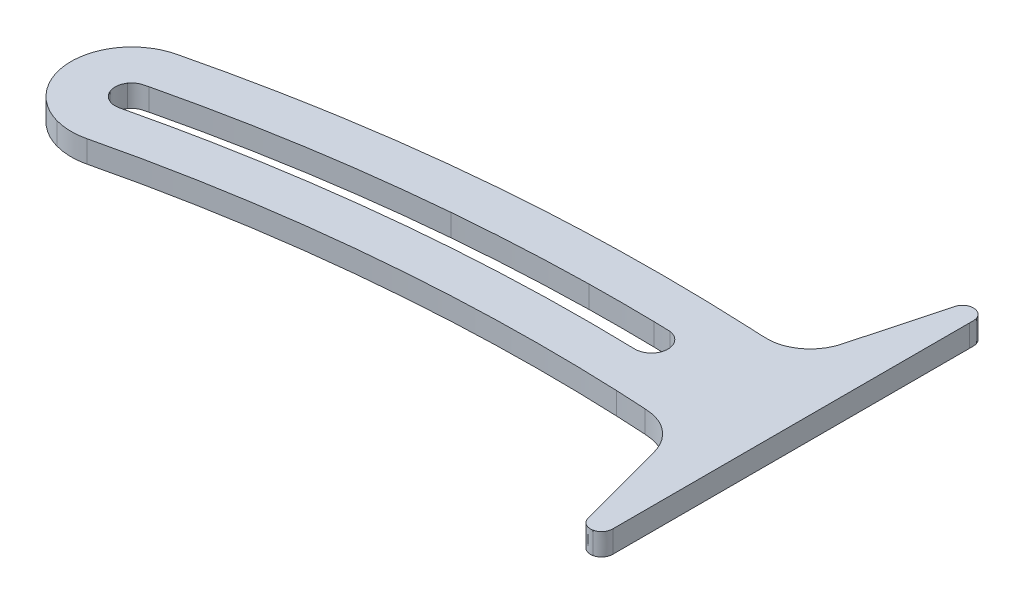
SolidWorks part; units mm, degrees
ref_plane "Front Plane" through (0, 0, 0) normal (0, 0, 1) x (1, 0, 0)
ref_plane "Top Plane" through (0, 0, 0) normal (0, 1, 0) x (1, 0, 0)
ref_plane "Right Plane" through (0, 0, 0) normal (1, 0, 0) x (0, 0, -1)
sketch "Imported Profile" plane through (0, 0, 0) normal (0, 1, 0) x (1, 0, 0)
  spline S0 degree 3 poles (12.8991, 25.236) (15.9171, 24.4093) (18.7007, 24.3473) (21.7531, 25.0501) knots 0 0 0 0 1 1 1 1
  spline S1 degree 3 poles (21.7531, 25.0501) (67.2422, 35.9573) (114.0335, 40.4773) (160.7696, 38.4929) knots 0 0 0 0 1 1 1 1
  spline S2 degree 3 poles (160.7696, 38.4929) (163.6635, 38.3689) (166.5574, 38.2174) (169.4444, 38.0449) knots 0 0 0 0 1 1 1 1
  spline S3 degree 3 poles (169.4444, 38.0449) (172.5863, 37.8589) (175.1081, 37.0734) (177.5541, 34.9719) knots 0 0 0 0 1 1 1 1
  spline S4 degree 3 poles (177.5541, 34.9719) (178.7254, 33.9728) (179.6419, 32.8428) (180.3929, 31.4993) knots 0 0 0 0 1 1 1 1
  spline S5 degree 3 poles (180.3929, 31.4993) (181.1026, 30.2177) (181.4953, 28.8603) (181.8674, 27.4685) knots 0 0 0 0 1 1 1 1
  spline S6 degree 3 poles (181.8674, 27.4685) (182.6184, 24.6642) (183.3694, 21.8599) (184.1205, 19.0625) knots 0 0 0 0 1 1 1 1
  spline S7 degree 3 poles (184.1205, 19.0625) (184.8715, 16.2582) (185.6225, 13.4539) (186.3735, 10.6495) knots 0 0 0 0 1 1 1 1
  spline S8 degree 3 poles (186.3735, 10.6495) (186.7457, 9.2508) (187.1246, 7.8521) (187.4967, 6.4465) knots 0 0 0 0 1 1 1 1
  spline S9 degree 3 poles (187.4967, 6.4465) (187.6827, 5.7506) (187.8756, 5.0478) (188.0617, 4.345) knots 0 0 0 0 1 1 1 1
  spline S10 degree 3 poles (188.0617, 4.345) (188.2477, 3.6491) (188.3786, 2.9463) (188.6335, 2.2642) knots 0 0 0 0 1 1 1 1
  spline S11 degree 3 poles (188.6335, 2.2642) (189.1847, 0.8172) (190.7006, -0.0165) (192.2233, 0.2798) knots 0 0 0 0 1 1 1 1
  spline S12 degree 3 poles (192.2233, 0.2798) (193.7874, 0.5968) (194.7796, 1.9335) (194.7796, 3.4975) knots 0 0 0 0 1 1 1 1
  spline S13 degree 3 poles (194.7796, 3.4975) (194.7796, 6.3983) (194.7796, 9.2991) (194.7796, 12.1998) knots 0 0 0 0 1 1 1 1
  spline S14 degree 3 poles (194.7796, 12.1998) (194.7796, 35.5507) (194.7796, 58.9084) (194.7796, 82.2593) knots 0 0 0 0 1 1 1 1
  spline S15 degree 3 poles (194.7796, 82.2593) (194.7796, 88.0608) (194.7796, 93.8624) (194.7796, 99.6708) knots 0 0 0 0 1 1 1 1
  spline S16 degree 3 poles (194.7796, 99.6708) (194.7796, 101.1178) (194.7796, 102.5716) (194.7796, 104.0185) knots 0 0 0 0 1 1 1 1
  spline S17 degree 3 poles (194.7796, 104.0185) (194.7796, 104.742) (194.7796, 105.4724) (194.7796, 106.1958) knots 0 0 0 0 1 1 1 1
  spline S18 degree 3 poles (194.7796, 106.1958) (194.7796, 106.9193) (194.8485, 107.6152) (194.6072, 108.3387) knots 0 0 0 0 1 1 1 1
  spline S19 degree 3 poles (194.6072, 108.3387) (194.1043, 109.7994) (192.6229, 110.6882) (191.0932, 110.4402) knots 0 0 0 0 1 1 1 1
  spline S20 degree 3 poles (191.0932, 110.4402) (190.2595, 110.3027) (189.6807, 109.9717) (189.1433, 109.3171) knots 0 0 0 0 1 1 1 1
  spline S21 degree 3 poles (189.1433, 109.3171) (188.6541, 108.7176) (188.5094, 108.0424) (188.3234, 107.3327) knots 0 0 0 0 1 1 1 1
  spline S22 degree 3 poles (188.3234, 107.3327) (186.8213, 101.731) (185.3193, 96.1292) (183.8172, 90.5206) knots 0 0 0 0 1 1 1 1
  spline S23 degree 3 poles (183.8172, 90.5206) (183.0662, 87.7232) (182.3909, 84.912) (181.5641, 82.1353) knots 0 0 0 0 1 1 1 1
  spline S24 degree 3 poles (181.5641, 82.1353) (180.7097, 79.2483) (178.8563, 76.7678) (176.3413, 75.121) knots 0 0 0 0 1 1 1 1
  spline S25 degree 3 poles (176.3413, 75.121) (172.2486, 72.4477) (169.1411, 73.0678) (164.7796, 73.2676) knots 0 0 0 0 1 1 1 1
  spline S26 degree 3 poles (164.7796, 73.2676) (145.3906, 74.1909) (126.0843, 74.1289) (106.7022, 73.0126) knots 0 0 0 0 1 1 1 1
  spline S27 degree 3 poles (106.7022, 73.0126) (83.2893, 71.6621) (60.2485, 68.6924) (37.2422, 64.1724) knots 0 0 0 0 1 1 1 1
  spline S28 degree 3 poles (37.2422, 64.1724) (29.3115, 62.6153) (21.4154, 60.9065) (13.5537, 58.9979) knots 0 0 0 0 1 1 1 1
  spline S29 degree 3 poles (13.5537, 58.9979) (13.4434, 58.9679) (13.3332, 58.9429) (13.2298, 58.9154) knots 0 0 0 0 1 1 1 1
  spline S30 degree 3 poles (13.2298, 58.9154) (13.0093, 58.8604) (12.7889, 58.7984) (12.5753, 58.7294) knots 0 0 0 0 1 1 1 1
  spline S31 degree 3 poles (12.5753, 58.7294) (12.1274, 58.5914) (11.6933, 58.4469) (11.2661, 58.2744) knots 0 0 0 0 1 1 1 1
  spline S32 degree 3 poles (11.2661, 58.2744) (10.3773, 57.9229) (9.5298, 57.5027) (8.7099, 57.0135) knots 0 0 0 0 1 1 1 1
  spline S33 degree 3 poles (8.7099, 57.0135) (6.9735, 55.9731) (5.5197, 54.726) (4.2313, 53.1688) knots 0 0 0 0 1 1 1 1
  spline S34 degree 3 poles (4.2313, 53.1688) (1.7439, 50.1716) (0.3383, 46.4302) (0.2281, 42.5373) knots 0 0 0 0 1 1 1 1
  spline S35 degree 3 poles (0.2281, 42.5373) (-0.0062, 34.5515) (5.2166, 27.4271) (12.8991, 25.236) knots 0 0 0 0 1 1 1 1
  spline S36 degree 3 poles (153.0044, 51.4685) (156.4908, 51.3706) (158.8886, 54.9191) (157.5036, 58.1161) knots 0 0 0 0 1 1 1 1
  spline S37 degree 3 poles (157.5036, 58.1161) (156.8353, 59.6595) (155.409, 60.7344) (153.7416, 60.948) knots 0 0 0 0 1 1 1 1
  spline S38 degree 3 poles (153.7416, 60.948) (153.2937, 61.01) (149.5386, 61.072) (149.0907, 61.079) knots 0 0 0 0 1 1 1 1
  spline S39 degree 3 poles (149.0907, 61.079) (142.8482, 61.196) (136.5988, 61.203) (130.3494, 61.094) knots 0 0 0 0 1 1 1 1
  spline S40 degree 3 poles (130.3494, 61.094) (117.7059, 60.8805) (105.1106, 60.212) (92.5154, 59.0889) knots 0 0 0 0 1 1 1 1
  spline S41 degree 3 poles (92.5154, 59.0889) (67.2422, 56.8358) (42.4581, 52.8051) (17.7706, 46.9484) knots 0 0 0 0 1 1 1 1
  spline S42 degree 3 poles (17.7706, 46.9484) (16.1652, 46.5694) (14.7734, 46.2387) (13.7329, 44.6953) knots 0 0 0 0 1 1 1 1
  spline S43 degree 3 poles (13.7329, 44.6953) (12.8234, 43.3517) (12.6649, 41.6499) (13.3057, 40.1547) knots 0 0 0 0 1 1 1 1
  spline S44 degree 3 poles (13.3057, 40.1547) (13.9672, 38.6044) (15.4072, 37.5226) (17.0816, 37.309) knots 0 0 0 0 1 1 1 1
  spline S45 degree 3 poles (17.0816, 37.309) (17.8808, 37.2055) (18.6112, 37.359) (19.3691, 37.5365) knots 0 0 0 0 1 1 1 1
  spline S46 degree 3 poles (19.3691, 37.5365) (20.127, 37.7225) (20.8849, 37.9015) (21.6429, 38.074) knots 0 0 0 0 1 1 1 1
  spline S47 degree 3 poles (21.6429, 38.074) (27.7269, 39.5002) (33.8316, 40.8094) (39.9708, 42.0151) knots 0 0 0 0 1 1 1 1
  spline S48 degree 3 poles (39.9708, 42.0151) (52.38, 44.4405) (64.8375, 46.4111) (77.3914, 47.9269) knots 0 0 0 0 1 1 1 1
  spline S49 degree 3 poles (77.3914, 47.9269) (102.5751, 50.9655) (127.6485, 52.1368) (153.0044, 51.4685) knots 0 0 0 0 1 1 1 1
extrude "Boss-Extrude1" add sketch "Imported Profile" along normal blind 6.35
